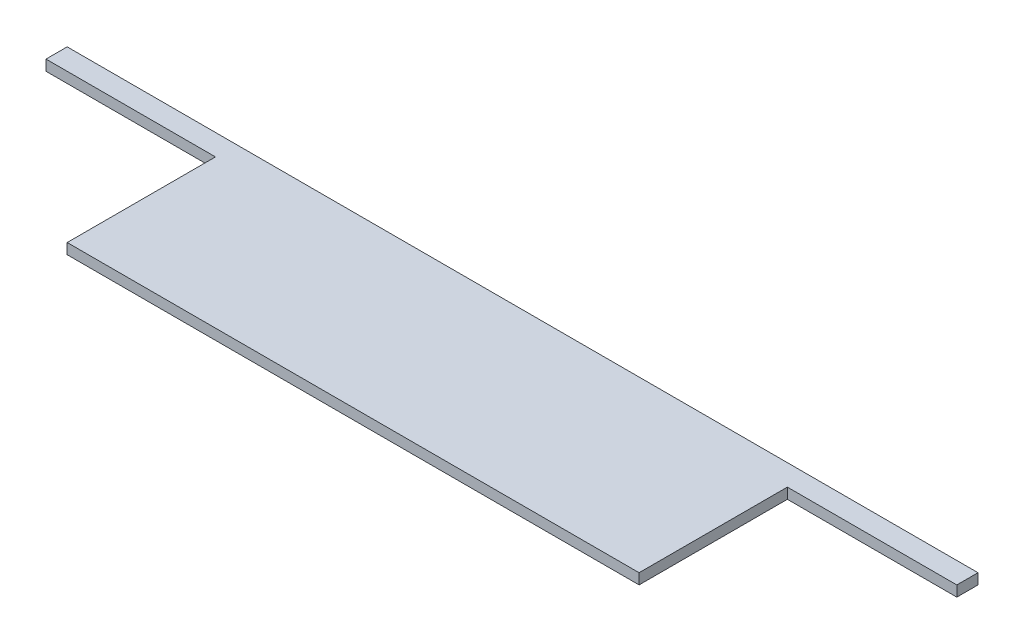
SolidWorks part; units mm, degrees
ref_plane "Front Plane" through (0, 0, 0) normal (0, 0, 1) x (1, 0, 0)
ref_plane "Top Plane" through (0, 0, 0) normal (0, 1, 0) x (1, 0, 0)
ref_plane "Right Plane" through (0, 0, 0) normal (1, 0, 0) x (0, 0, -1)
sketch "Sketch1" plane through (0, 0, 0) normal (0, 1, 0) x (1, 0, 0)
  line L0 (-136.525, 19.05) -> (-85.725, 19.05)
  line L1 (-136.525, -25.4) -> (136.525, -25.4)
  line L2 (-136.525, -25.4) -> (-136.525, 25.4)
  line L3 (-136.525, 25.4) -> (136.525, 25.4)
  line L4 (136.525, -25.4) -> (136.525, 25.4)
  line L5 (-136.525, -25.4) -> (136.525, 25.4) construction
  line L6 (-136.525, 25.4) -> (136.525, -25.4) construction
  line L7 (-85.725, 19.05) -> (-85.725, -25.4)
  line L8 (136.525, 19.05) -> (85.725, 19.05)
  line L9 (85.725, 19.05) -> (85.725, -25.4)
  point P0 (0, 0)
  dimension "D1" = 50.8
  dimension "D2" = 273.05
  dimension "D3" = 44.45
  dimension "D4" = 50.8
extrude "Boss-Extrude1" add sketch "Sketch1" along normal blind 3.175 contours L9 L8 L4 L3 L2 L0 L7 L1 region at (0, 0, -1.5328)
